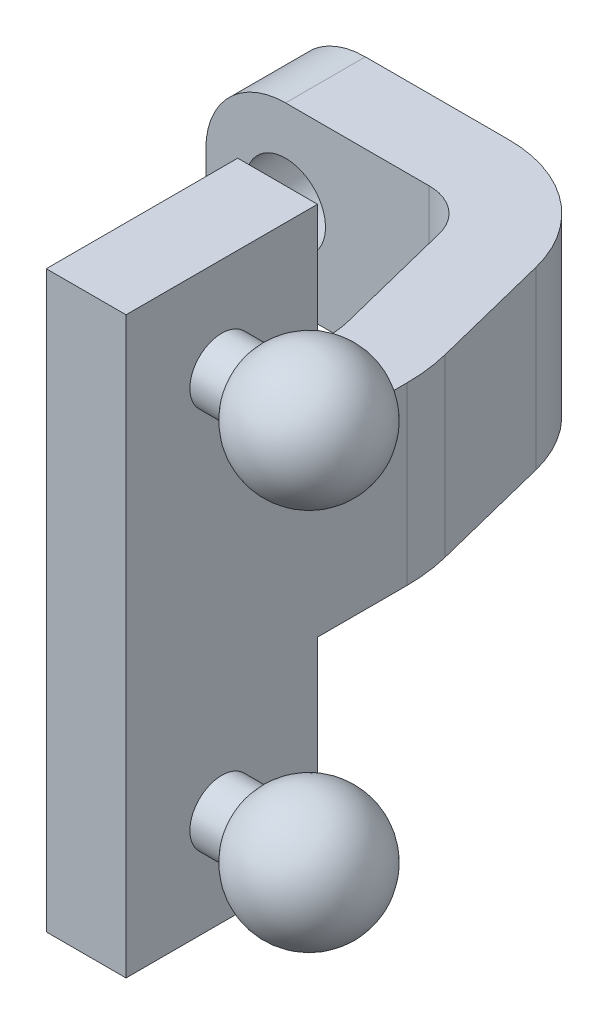
SolidWorks part; units mm, degrees
ref_plane "前视基准面" through (0, 0, 0) normal (0, 0, 1) x (1, 0, 0)
ref_plane "上视基准面" through (0, 0, 0) normal (0, 1, 0) x (1, 0, 0)
ref_plane "右视基准面" through (0, 0, 0) normal (1, 0, 0) x (0, 0, -1)
other "Configuration Table"
sketch "草图1" plane through (0, 0, 0) normal (0, 1, 0) x (1, 0, 0)
  line L0 (0, 0) -> (7, 0)
  line L1 (12, -8.1977) -> (12, -17)
  line L2 (0, -2.5) -> (7, -2.5)
  line L3 (9.5, -8.1977) -> (9.5, -17)
  line L4 (9.5, -17) -> (12, -17)
  line L5 (0, 0) -> (0, -2.5)
  line L6 (10.8804, -3.0293) -> (11.8318, -6.8324)
  line L7 (8.4552, -3.636) -> (9.4065, -7.4391)
  arc A0 (7, 0) -> (10.8804, -3.0293) centre (7, -4) cw
  arc A3 (7, -2.5) -> (8.4552, -3.636) centre (7, -4) cw
  arc A6 (11.1652, -3.9314) -> (12, -8.1977) centre (0.6805, -8.1977) cw construction
  arc A7 (10.8804, -3.0293) -> (11.1652, -3.9314) centre (18.4481, -1.1361) ccw construction
  arc A8 (8.4552, -3.636) -> (8.8414, -4.8535) centre (18.4481, -1.1361) ccw construction
  arc A9 (8.8414, -4.8535) -> (9.5, -8.1977) centre (0.6805, -8.1977) cw construction
  arc A10 (11.8318, -6.8324) -> (12, -8.1977) centre (6.374, -8.1977) cw
  arc A11 (9.5, -8.1977) -> (9.4065, -7.4391) centre (6.374, -8.1977) ccw
  dimension "D1" = 2.5
  dimension "D3" = 4
  dimension "D4" = 12
  dimension "D2" = 7
  dimension "D6" = 17
extrude "凸台-拉伸1" add sketch "草图1" along normal mid plane 5.5
sketch "草图2" plane through (0, 0, 0) normal (0, 0, -1) x (-1, 0, 0)
  line L0 (0, 2.75) -> (0, -2.75) construction
  circle A0 centre (-2.5, 0) radius 1.25
  point P5 (0, 0)
  dimension "D1" = 2.5
  dimension "D2" = 2.5
extrude "切除-拉伸1" cut sketch "草图2" against normal blind 10
fillet "圆角2" radius 2.5 2 edges at (0, -2.75, 1.25) (0, 2.75, 1.25)
sketch "草图4" plane through (9.5, 0, 0) normal (-1, 0, 0) x (0, 0, 1)
  line L0 (17, 2.75) -> (17, -2.75) construction
  line L1 (11, 9) -> (17, 9)
  line L2 (11, 9) -> (11, -9)
  line L3 (11, -9) -> (17, -9)
  line L4 (17, 9) -> (17, -9)
  line L5 (11, 9) -> (17, -9) construction
  line L6 (11, -9) -> (17, 9) construction
  point P0 (14, 0)
  dimension "D1" = 18
  dimension "D2" = 6
extrude "凸台-拉伸2" add sketch "草图4" against normal up to surface (2.5 mm away) up to face at (12, 0, 12.5989)
sketch "草图5" plane through (12, 0, 0) normal (1, 0, 0) x (0, 0, -1)
  line L0 (-11, 9) -> (-17, 9) construction
  line L1 (-11, 2.75) -> (-11, 9) construction
  circle A0 centre (-14, 6) radius 1
  dimension "D1" = 2
  dimension "D2" = 3
  dimension "D3" = 3
extrude "凸台-拉伸3" add sketch "草图5" along normal blind 1
ref_axis "基准轴1" through (13, 6, 14) along (-1, 0, 0)
ref_plane "基准面1" through (0, 0, 14) normal (0, 0, -1) x (-1, 0, 0)
sketch "草图6" plane through (0, 0, 14) normal (0, 0, -1) x (-1, 0, 0)
  line L0 (-13, 6) -> (-16.7321, 6)
  line L1 (-13, 7) -> (-13, 5) construction
  line L2 (-13, 6) -> (-12, 6) construction
  line L3 (-13, 6) -> (-13, 7)
  line L4 (-12, 7) -> (-13, 7) construction
  arc A0 (-13, 7) -> (-16.7321, 6) centre (-14.7321, 6) ccw
  dimension "D1" = 4
revolve "旋转1" add sketch "草图6" angle 360 about L0
mirror "镜向1" about plane through (0, 0, 0) normal (0, 1, 0) of "凸台-拉伸3", "旋转1"
